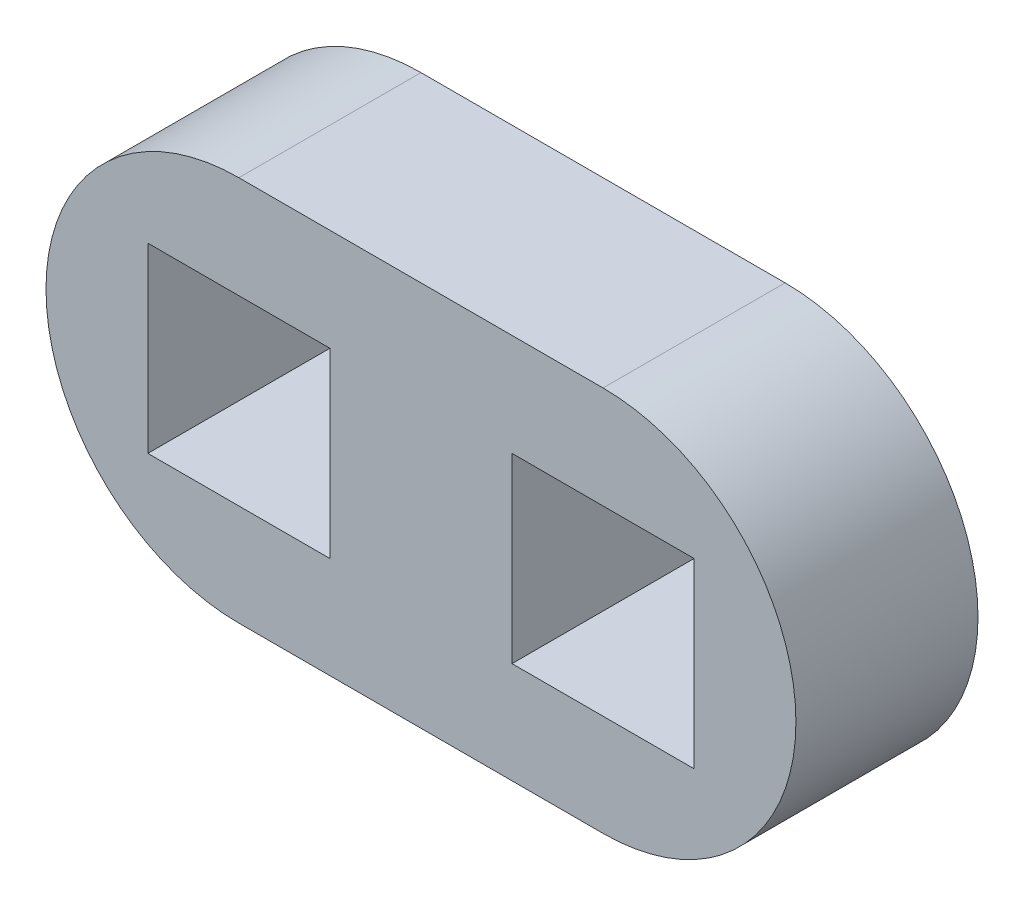
SolidWorks part; units mm, degrees
ref_plane "Front Plane" through (0, 0, 0) normal (0, 0, 1) x (1, 0, 0)
ref_plane "Top Plane" through (0, 0, 0) normal (0, 1, 0) x (1, 0, 0)
ref_plane "Right Plane" through (0, 0, 0) normal (1, 0, 0) x (0, 0, -1)
sketch "Sketch1" plane through (0, 0, 0) normal (0, 0, 1) x (1, 0, 0)
  line L0 (372.6217, 118.0022) -> (384.6105, 118.0022) construction
  line L1 (387.6077, 114.994) -> (381.6133, 114.994)
  line L2 (387.6077, 114.994) -> (387.6077, 120.9884)
  line L3 (387.6077, 120.9884) -> (381.6133, 120.9884)
  line L4 (381.6133, 114.994) -> (381.6133, 120.9884)
  line L5 (375.6189, 120.9884) -> (369.6245, 120.9884)
  line L6 (375.6189, 120.9884) -> (375.6189, 114.994)
  line L7 (375.6189, 114.994) -> (369.6245, 114.994)
  line L8 (369.6245, 120.9884) -> (369.6245, 114.994)
  line L9 (372.6217, 124.3522) -> (384.6105, 124.3522)
  line L10 (372.6217, 111.6522) -> (384.6105, 111.6522)
  arc A0 (372.6217, 124.3522) -> (372.6217, 111.6522) centre (372.6217, 118.0022) ccw
  arc A1 (384.6105, 111.6522) -> (384.6105, 124.3522) centre (384.6105, 118.0022) ccw
  point P14 (378.6161, 118.0022)
extrude "Boss-Extrude1" add sketch "Sketch1" along normal blind 5.9944
